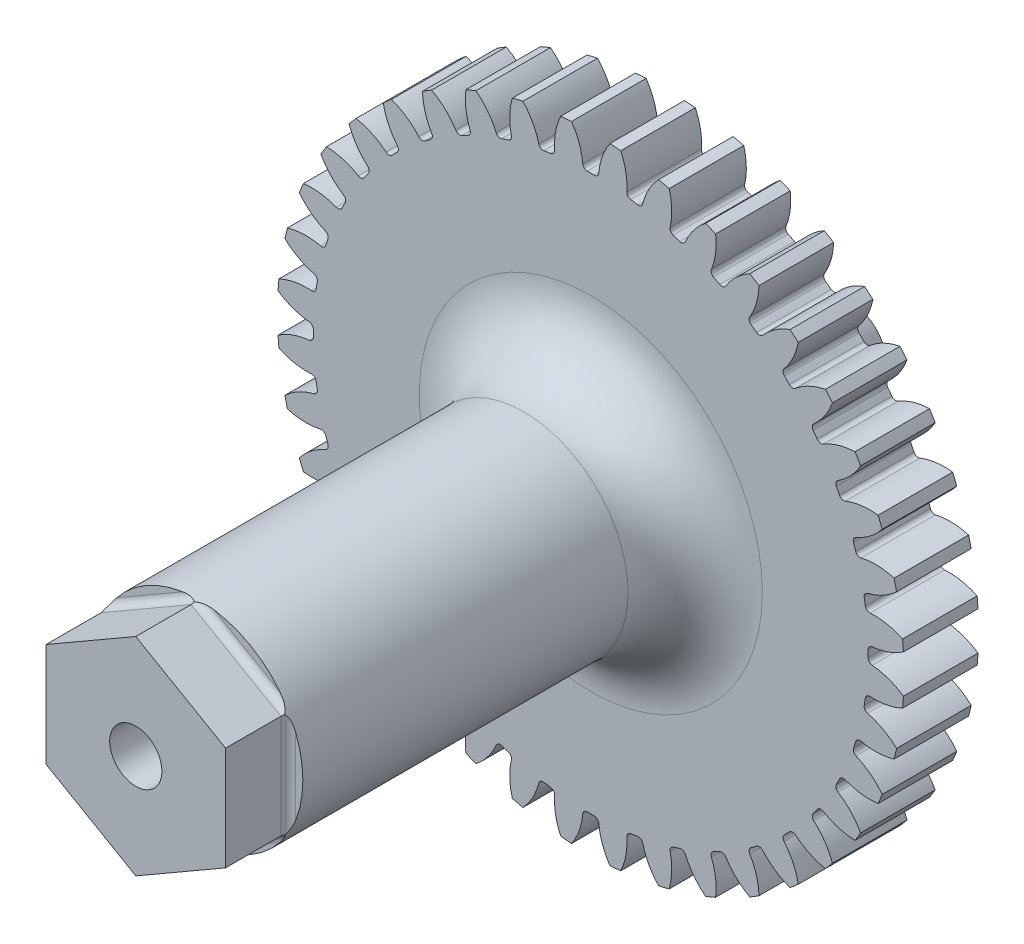
SolidWorks part; units mm, degrees
ref_plane "Front Plane" through (0, 0, 0) normal (0, 0, 1) x (1, 0, 0)
ref_plane "Top Plane" through (0, 0, 0) normal (0, 1, 0) x (1, 0, 0)
ref_plane "Right Plane" through (0, 0, 0) normal (1, 0, 0) x (0, 0, -1)
sketch "Sketch1" plane through (0, 0, 0) normal (0, 0, 1) x (1, 0, 0)
  circle A2 centre (0, 0) radius 20
  circle A3 centre (0, 0) radius 21
  circle A4 centre (0, 0) radius 18.6
  dimension "D1" = 40
  dimension "D2" = 42
  dimension "D3" = 2.4
extrude "Boss-Extrude1" add sketch "Sketch1" along normal mid plane 5 contours A3
sketch "Sketch3" plane through (0, 0, 2.5) normal (0, 0, 1) x (1, 0, 0)
  line L0 (0, 0) -> (0, 21) construction
  line L1 (-0.7852, 19.9846) -> (0.7852, 19.9846) construction
  line L2 (0, 0) -> (-0.5197, 18.5927) construction
  line L3 (0, 17.8273) -> (-1.5001, 21.9488) construction
  line L4 (0, 0) -> (1.6476, 20.9353) construction
  line L5 (0.7852, 19.9846) -> (2.3507, 19.8614) construction
  circle A0 centre (0, 0) radius 21 construction
  arc A1 (-2.1396, 21.8957) -> (-0.5197, 18.5927) centre (-4.9494, 18.4689) cw
  arc A2 (2.1396, 21.8957) -> (0.5197, 18.5927) centre (4.9494, 18.4689) ccw
  circle A3 centre (0, 0) radius 18.6 construction
  arc A4 (0.5197, 18.5927) -> (-0.5197, 18.5927) centre (0, 0) ccw
  circle A5 centre (0, 0) radius 20 construction
  circle A6 centre (0, 0) radius 21 construction
  circle A7 centre (0, 0) radius 22
  arc A8 (2.1396, 21.8957) -> (-2.1396, 21.8957) centre (0, 0) ccw
  dimension "D2" = 20
  dimension "D3" = 4.5
extrude "Cut-Extrude1" cut sketch "Sketch3" against normal through all both and the other way through all
fillet "Fillet1" radius 0.3 2 edges at (0.5197, 18.5927, 0) (-0.5197, 18.5927, 0)
pattern_circular "CirPattern1" count 40 over 360 about axis through (0, 0, 2.5) along (0, 0, -1) of "Cut-Extrude1", "Fillet1"
sketch "Sketch4" plane through (0, 0, 2.5) normal (0, 0, 1) x (1, 0, 0)
  circle A0 centre (0, 0) radius 7
  dimension "D1" = 14
extrude "Wheelshaft" add sketch "Sketch4" along normal blind 26.3
sketch "Sketch5" plane through (0, 0, -2.5) normal (0, 0, -1) x (-1, 0, 0)
  circle A0 centre (0, 0) radius 2.8
  dimension "D1" = 5.6
extrude "Boss-Extrude3" add sketch "Sketch5" along normal blind 12.43
fillet "Fillet3" radius 7.4 1 edges at (2.8, 0, -2.5)
chamfer "Chamfer1" distance 1.5 angle 15 1 edges at (-2.8, 0, -14.93) first distance on face at (2.8, 0, -9.9)
fillet "Fillet4" radius 4.5 1 edges at (7, 0, 2.5)
sketch "Sketch6" plane through (0, 0, 28.8) normal (0, 0, 1) x (1, 0, 0)
  line L1 (0, 6.95) -> (-6.0189, 3.475)
  line L2 (-6.0189, 3.475) -> (-6.0189, -3.475)
  line L3 (-6.0189, -3.475) -> (0, -6.95)
  line L4 (0, -6.95) -> (6.0189, -3.475)
  line L5 (6.0189, -3.475) -> (6.0189, 3.475)
  line L6 (6.0189, 3.475) -> (0, 6.95)
  circle A0 centre (0, 0) radius 6.95 construction
  dimension "D1" = 13.9
extrude "Boss-Extrude4" add sketch "Sketch6" along normal blind 4.2
sketch "Sketch7" plane through (0, 0, 33) normal (0, 0, 1) x (1, 0, 0)
  circle A0 centre (0, 0) radius 1.75
  dimension "D1" = 3.5
extrude "Cut-Extrude2" cut sketch "Sketch7" against normal blind 7
fillet "Fillet5" radius 0.5 6 edges at (3.0094, 5.2125, 28.8) (-6.0189, 0, 28.8) (-3.0094, -5.2125, 28.8) (3.0094, -5.2125, 28.8) (6.0189, 0, 28.8) (-3.0094, 5.2125, 28.8)
equation "\"Module\"= 1mm"
equation "\"Number of Teeth\"= 40"
equation "\"D1@Sketch1\"=\"Module\" * \"Number of Teeth\""
equation "\"D2@Sketch1\"=(\"Number of Teeth\" + 2) * \"Module\""
equation "\"D3@Sketch1\"=\"Module\" * if( \"Module\"=>1.25,2.25,2.4)"
equation "\"D3@Sketch3\"=180 / \"Number of Teeth\""
equation "\"D1@Fillet1\"=0.3 * \"Module\""
equation "\"D1@CirPattern1\"=\"Number of Teeth\""
